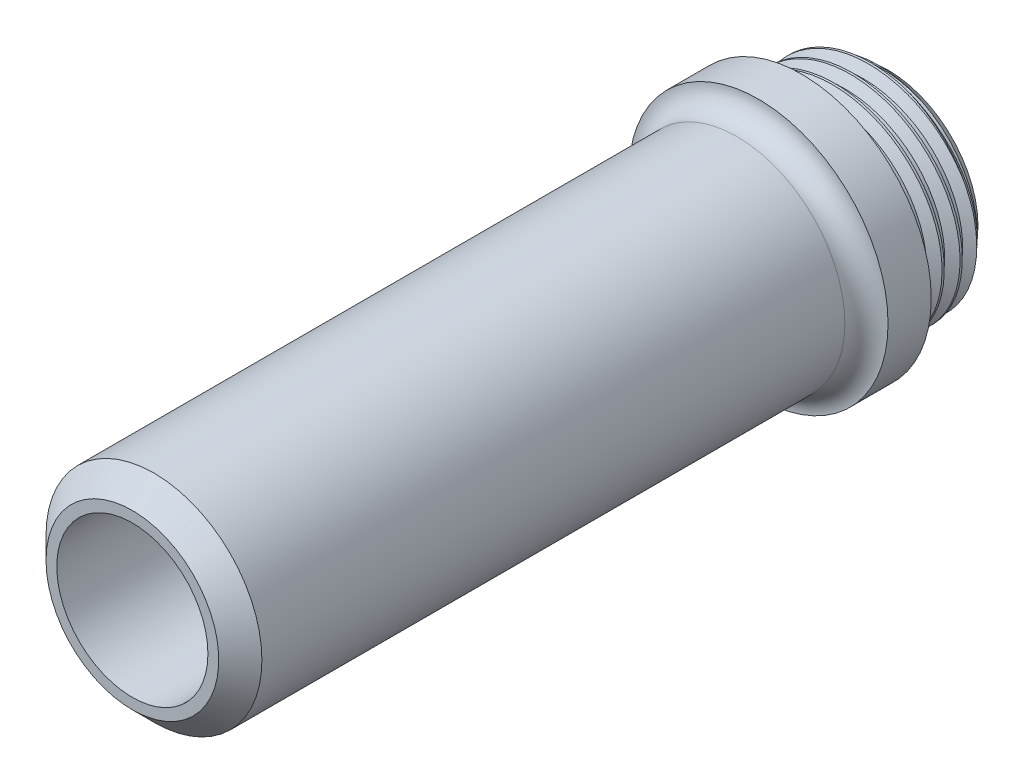
SolidWorks part; units mm, degrees
material "Plain Carbon Steel"
ref_plane "Front Plane" through (0, 0, 0) normal (0, 0, 1) x (1, 0, 0)
ref_plane "Top Plane" through (0, 0, 0) normal (0, 1, 0) x (1, 0, 0)
ref_plane "Right Plane" through (0, 0, 0) normal (1, 0, 0) x (0, 0, -1)
sketch "Sketch1" plane through (0, 0, 0) normal (0, 0, 1) x (1, 0, 0)
  circle A0 centre (0, 0) radius 7.62
  dimension "D1" = 15.24
extrude "Boss-Extrude1" add sketch "Sketch1" along normal blind 2.54
sketch "Sketch2" plane through (0, 0, 0) normal (0, 0, -1) x (-1, 0, 0)
  circle A0 centre (0, 0) radius 6.35
  dimension "D1" = 12.7
extrude "Boss-Extrude2" add sketch "Sketch2" along normal blind 5.08 and the other way blind 39.37
thread "Thread1" pitch 1.0583 method cut profile "Thread Profile1" start angle 0, offset 0, length 5.461, pitch 1.0583, diameter 12.7
ref_plane "Plane1" through (6.35, 0, -5.08) normal (0, -1, 0) x (1, 0, 0)
sketch "Thread Profile1" plane through (6.35, 0, -5.08) normal (0, -1, 0) x (1, 0, 0)
  line L0 (0, 0) -> (0, 1.0583) construction
  line L11 (0, 0) -> (0, 0.926)
  line L12 (0, 0.926) -> (-0.5728, 0.5953)
  line L13 (-0.5728, 0.5953) -> (-0.5728, 0.3307)
  line L15 (-0.5728, 0.3307) -> (0, 0)
  line L17 (-0.5728, 0.463) -> (0, 0.463) construction
  point P2 (0, 0)
  dimension "Pitch" = 1.0583
  dimension "Profile_Angle" = 60
  dimension "Profile_Land" = 0.2646
  dimension "Profile_Height" = 0.5728
sketch "Sketch6" plane through (0, 0, 0) normal (0, 1, 0) x (1, 0, 0)
  line L0 (0, 0) -> (0, 5.08) construction
  line L1 (6.35, 5.08) -> (-6.35, 5.08) construction
  line L2 (4.699, 5.715) -> (6.477, 3.81)
  line L3 (6.477, 3.81) -> (6.477, 5.715)
  line L4 (6.477, 5.715) -> (4.699, 5.715)
  dimension "D1" = 4.699
  dimension "D2" = 1.778
  dimension "D3" = 1.905
  dimension "D4" = 0.635
revolve "Cut-Revolve1" cut sketch "Sketch6" angle 360 about L0
fillet "Fillet1" radius 1.27 1 edges at (6.35, 0, 2.54)
chamfer "Chamfer1" distance 1.27 angle 45 1 edges at (-6.35, 0, 39.37)
sketch "Sketch7" plane through (0, 0, 39.37) normal (0, 0, 1) x (1, 0, 0)
  circle A0 centre (0, 0) radius 4.445
  dimension "D1" = 8.89
extrude "Cut-Extrude1" cut sketch "Sketch7" against normal through all
